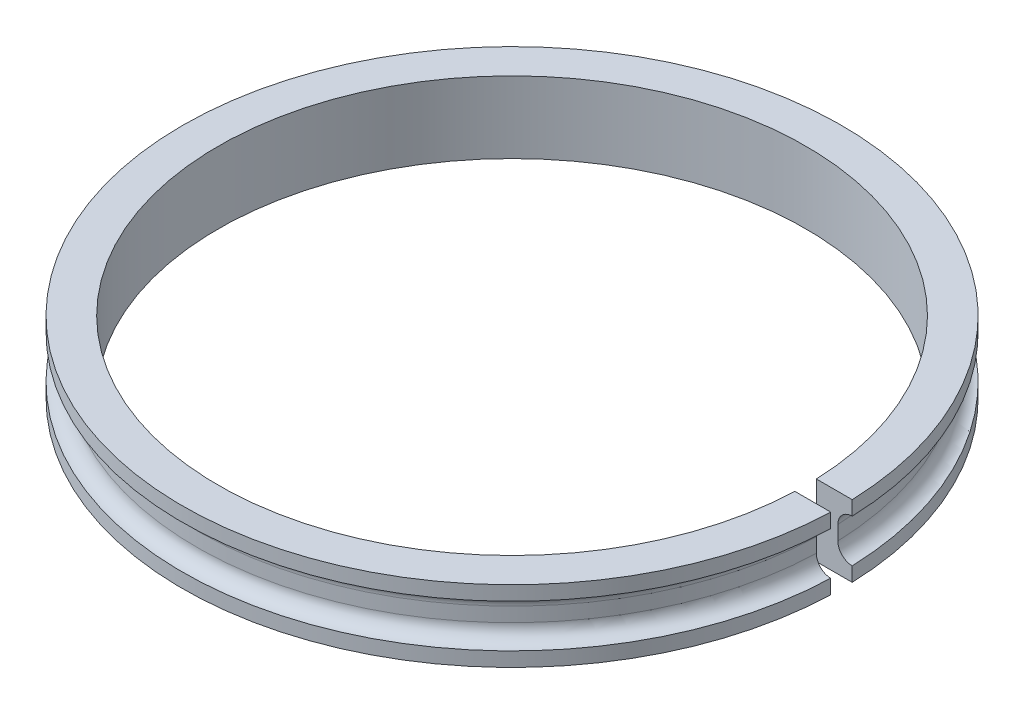
SolidWorks part; units mm, degrees
ref_plane "Front Plane" through (0, 0, 0) normal (0, 0, 1) x (1, 0, 0)
ref_plane "Top Plane" through (0, 0, 0) normal (0, 1, 0) x (1, 0, 0)
ref_plane "Right Plane" through (0, 0, 0) normal (1, 0, 0) x (0, 0, -1)
sketch "Sketch1" plane through (0, 0, 0) normal (0, 1, 0) x (1, 0, 0)
  circle A3 centre (-93, 0) radius 41
  circle A4 centre (-93, 0) radius 41
  circle A5 centre (-93, 0) radius 46
  dimension "D1" = 2
extrude "Boss-Extrude1" add sketch "Sketch1" along normal blind 10
sketch "Sketch2" plane through (0, 0, 0) normal (0, 1, 0) x (1, 0, 0)
  line L1 (-57.853, 1.5) -> (-44.147, 1.5)
  line L2 (-57.853, 1.5) -> (-57.853, -1.5)
  line L3 (-57.853, -1.5) -> (-44.147, -1.5)
  line L4 (-44.147, 1.5) -> (-44.147, -1.5)
  line L5 (-57.853, 1.5) -> (-44.147, -1.5) construction
  line L6 (-57.853, -1.5) -> (-44.147, 1.5) construction
  point P0 (-51, 0)
  dimension "D1" = 3
extrude "Cut-Extrude2" cut sketch "Sketch2" along normal through all
ref_plane "Plane1" through (0, 2, 0) normal (0, -1, 0) x (-1, 0, 0)
sketch "Sketch3" plane through (0, 2, 0) normal (0, -1, 0) x (-1, 0, 0)
  circle A0 centre (93, 0) radius 44
  circle A1 centre (93, 0) radius 47
  dimension "D1" = 3
extrude "Cut-Extrude3" cut sketch "Sketch3" against normal blind 6
fillet "Fillet1" radius 2 1 edges at (-137, 8, 0) type face fillet first side face at (-93.0125, 8, 0) second side face at (-93.0128, 5, 0)
fillet "Fillet2" radius 2 1 edges at (-137, 2, 0) type face fillet first side face at (-93.0128, 4, 0) second side face at (-93.0125, 2, 0)
